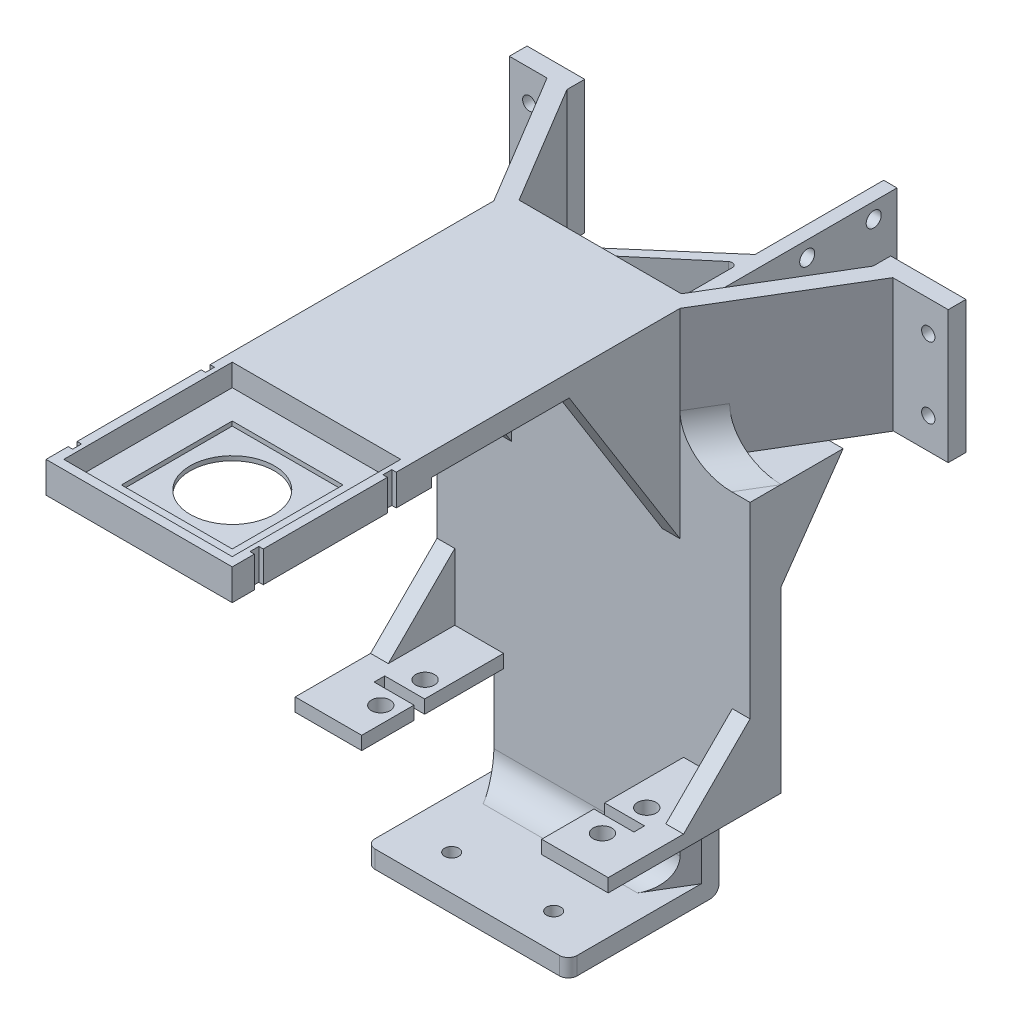
SolidWorks part; units mm, degrees
ref_plane "前视基准面" through (0, 0, 0) normal (0, 0, 1) x (1, 0, 0)
ref_plane "上视基准面" through (0, 0, 0) normal (0, 1, 0) x (1, 0, 0)
ref_plane "右视基准面" through (0, 0, 0) normal (1, 0, 0) x (0, 0, -1)
other "Configuration Table"
sketch "草图1" plane through (0, 0, 0) normal (0, 0, 1) x (1, 0, 0)
  line L0 (0, 22.8958) -> (0, -22.7413) construction
  line L1 (-34.5, 14.6332) -> (-47.5, 14.6332)
  line L2 (-47.5, 14.6332) -> (-47.5, -15.3668)
  line L3 (-47.5, -15.3668) -> (-34.5, -15.3668)
  line L5 (-37.5, 29.7319) -> (-37.5, -30.5186) construction
  line L6 (-34.5, 14.6332) -> (-34.5, -15.3668)
  line L11 (38.5, 14.6332) -> (51.5, 14.6332)
  line L12 (51.5, 14.6332) -> (51.5, -15.2668)
  line L13 (51.5, -15.2668) -> (38.5, -15.2668)
  line L14 (38.5, -15.2668) -> (38.5, 14.6332)
  circle A0 centre (-43, 7.6832) radius 1.5
  circle A1 centre (-43, -8.3168) radius 1.5
  circle A4 centre (47, -8.3168) radius 1.5
  circle A5 centre (47, 7.6832) radius 1.5
  dimension "D3" = 3
  dimension "D4" = 6.95
  dimension "D5" = 16
  dimension "D6" = 3
  dimension "D1" = 3
  dimension "D9" = 90
  dimension "D10" = 3
  dimension "D11" = 4.5
  dimension "D12" = 4.5
  dimension "D13" = 8.5
  dimension "D14" = 6.95
  dimension "D2" = 30
  dimension "D7" = 37.5
  dimension "D8" = 3
extrude "凸台-拉伸1" add sketch "草图1" along normal blind 4
sketch "草图2" plane through (0, 0, 0) normal (0, 1, 0) x (1, 0, 0)
  line L0 (0, 28.3363) -> (0, -34) construction
  line L1 (-39, -4) -> (-21, -34)
  line L2 (-34.5, -4) -> (-47.5, -4) construction
  line L3 (-21, -34) -> (21, -34)
  line L4 (-34.5, -4) -> (-18.3, -31)
  line L5 (-18.3, -31) -> (18.3, -31)
  line L6 (-39, -4) -> (-34.5, -4)
  line L7 (39, -4) -> (34.5, -4)
  line L8 (39, -4) -> (21, -34)
  line L9 (34.5, -4) -> (18.3, -31)
  point P7 (-41, -4)
  point P14 (0, -31)
  dimension "D1" = 21
  dimension "D2" = 30
  dimension "D3" = 2
  dimension "D4" = 3
extrude "凸台-拉伸2" add sketch "草图2" along normal up to surface and the other way up to surface up to face at (-41, 14.6332, 2) other way up to face at (-41, -15.3668, 2)
sketch "草图6" plane through (0, -15.3668, 0) normal (0, -1, 0) x (1, 0, 0)
  line L1 (-21, 31) -> (21.0707, 31)
  line L3 (-18.3, 31) -> (18.3, 31) construction
  line L5 (-21, 34) -> (21, 34)
  line L6 (-21, 34) -> (-22.8, 31)
  line L7 (-21, 34) -> (-39, 4) construction
  line L8 (-22.8, 31) -> (-21, 31)
  line L9 (21.0707, 31) -> (22.8, 31)
  line L10 (39, 4) -> (21, 34) construction
  line L11 (22.8, 31) -> (21, 34)
extrude "凸台-拉伸4" add sketch "草图6" along normal blind 87
sketch "草图8" plane through (0, 0, 34) normal (0, 0, 1) x (1, 0, 0)
  line L0 (-22.8, -102.3668) -> (-22.8, -98.3668)
  line L1 (-22.8, -102.3668) -> (-22.8, -15.3668) construction
  line L2 (-22.8, -98.3668) -> (22.8, -98.3668)
  line L3 (22.8, -102.3668) -> (22.8, -15.3668) construction
  line L4 (22.8, -98.3668) -> (22.8, -102.3668)
  line L5 (22.8, -102.3668) -> (-22.8, -102.3668)
  dimension "D1" = 4
extrude "凸台-拉伸5" add sketch "草图8" along normal blind 30 from offset 3 offset against normal yes
fillet "圆角1" radius 6 1 edges at (0, -98.3668, 34)
sketch "草图10" plane through (0, 0, 31) normal (0, 0, -1) x (-1, 0, 0)
  line L0 (0, 22.2529) -> (0, -15.95) construction
  line L1 (-13.945, 9.6332) -> (-13.945, -12.3668)
  line L3 (18.3, 14.6332) -> (-18.3, 14.6332) construction
  line L4 (-13.945, -12.3668) -> (-16.945, -12.3668)
  line L5 (-16.945, -12.3668) -> (-16.945, 9.6332)
  line L6 (-16.945, 9.6332) -> (-13.945, 9.6332)
  dimension "D1" = 13.945
  dimension "D2" = 5
  dimension "D3" = 22
  dimension "D4" = 3
extrude "凸台-拉伸6" add sketch "草图10" along normal blind 50
sketch "草图13" plane through (13.945, 0, 0) normal (-1, 0, 0) x (0, 0, 1)
  line L1 (-11.75, -47.2714) -> (-11.75, 9.6332) construction
  line L2 (-11.75, -143.0278) -> (-11.75, -111.0278) construction
  line L3 (-19, 9.6332) -> (31, 9.6332) construction
  line L4 (-0.75, -113.0828) -> (-0.75, 9.6332) construction
  line L5 (-19, -1.3668) -> (-27.146, -1.3668) construction
  line L6 (-19, -12.3668) -> (-19, 9.6332) construction
  line L7 (-6.25, -1.9157) -> (-6.25, -9.7031) construction
  circle A0 centre (-13.75, 6.1332) radius 1.7
  circle A1 centre (-13.75, -8.8668) radius 1.7
  circle A2 centre (1.25, 6.1332) radius 1.7
  circle A3 centre (1.25, -8.8668) radius 1.7
  point P21 (-23.073, -1.3668)
  dimension "D1" = 3.4
  dimension "D4" = 7.5
  dimension "D5" = 15
  dimension "D6" = 15
  dimension "D7" = 7.5
  dimension "D2" = 15
  dimension "D3" = 15
  dimension "D8" = 5.5
extrude "切除-拉伸3" cut sketch "草图13" against normal blind 4
fillet "圆角3" radius 6 1 edges at (13.945, -1.3668, 31)
sketch "草图14" plane through (0, -98.3668, 0) normal (0, 1, 0) x (1, 0, 0)
  line L0 (0, -62.8301) -> (0, -20.3908) construction
  line L2 (22.8, -61) -> (-22.8, -61) construction
  circle A0 centre (-11.5, -53) radius 1.6
  circle A1 centre (11.5, -53) radius 1.6
  dimension "D1" = 3.2
  dimension "D2" = 11.5
  dimension "D3" = 3.2
  dimension "D4" = 11.5
  dimension "D5" = 8
extrude "切除-拉伸4" cut sketch "草图14" against normal blind 10
sketch "草图15" plane through (0, 0, 31) normal (0, 0, -1) x (-1, 0, 0)
  line L24 (18.8, -72.6668) -> (18.8, -75.6668)
  line L25 (18.8, -75.6668) -> (33.8, -75.6668)
  line L26 (33.8, -75.6668) -> (33.8, -72.6668)
  line L27 (33.8, -72.6668) -> (18.8, -72.6668)
  line L28 (-21.8, -72.6668) -> (-21.8, -75.6668)
  line L29 (-21.8, -75.6668) -> (-36.8, -75.6668)
  line L30 (-36.8, -75.6668) -> (-36.8, -72.6668)
  line L31 (-36.8, -72.6668) -> (-21.8, -72.6668)
  dimension "D2" = 3
sketch "草图22" plane through (0, 0, 34) normal (0, 0, 1) x (1, 0, 0)
  line L0 (-21, 14.6332) -> (-21, 9.6332)
  line L1 (-21, 14.6332) -> (-21, -92.3668) construction
  line L2 (-21, 9.6332) -> (21, 9.6332)
  line L3 (21, 14.6332) -> (21, -92.3668) construction
  line L4 (21, 9.6332) -> (21, 14.6332)
  line L5 (21, 14.6332) -> (-21, 14.6332)
  dimension "D1" = 5
extrude "凸台-拉伸13" add sketch "草图22" along normal blind 90
sketch "草图23" plane through (0, 14.6332, 0) normal (0, 1, 0) x (1, 0, 0)
  line L0 (0, -76.1625) -> (0, -150.2681) construction
  line L1 (-19, -95) -> (19, -95)
  line L2 (19, -95) -> (19, -133)
  line L3 (19, -133) -> (-19, -133)
  line L4 (21, -124) -> (-21, -124) construction
  line L5 (-19, -95) -> (-19, -133)
  line L6 (-21, -93) -> (-21, -135)
  line L7 (21, -135) -> (-21, -135)
  line L8 (21, -93) -> (21, -135)
  line L9 (-21, -93) -> (21, -93)
  point P10 (0, -95)
  point P11 (0, -133)
  dimension "D1" = 38
  dimension "D2" = 19
  dimension "D3" = 9
  dimension "D4" = 2
extrude "凸台-拉伸14" add sketch "草图23" against normal blind 5
sketch "草图24" plane through (0, 14.6332, 0) normal (0, 1, 0) x (1, 0, 0)
  line L0 (0, -116.507) -> (0, -139.6912) construction
  line L1 (-19, -133) -> (19, -133)
  line L2 (19, -133) -> (19, -95)
  line L3 (19, -95) -> (-19, -95)
  line L4 (-19, -95) -> (-19, -133)
  dimension "D1" = 38
extrude "切除-拉伸6" cut sketch "草图24" against normal blind 5
sketch "草图26" plane through (0, 0, 95) normal (0, 0, 1) x (1, 0, 0)
  line L0 (-21, 9.6332) -> (-21, 7.6332)
  line L1 (-21, 9.6332) -> (-21, -92.3668) construction
  line L2 (-21, 7.6332) -> (21, 7.6332)
  line L3 (21, 9.6332) -> (21, -92.3668) construction
  line L4 (21, 7.6332) -> (21, 9.6332)
  line L5 (21, 9.6332) -> (-21, 9.6332)
  dimension "D1" = 2
extrude "凸台-拉伸17" add sketch "草图26" along normal blind 40 and the other way blind 5
sketch "草图27" plane through (0, 9.6332, 0) normal (0, 1, 0) x (1, 0, 0)
  line L0 (-19, -114) -> (19, -114) construction
  line L1 (-19, -95) -> (-19, -133) construction
  line L2 (19, -133) -> (19, -95) construction
  line L3 (0, -95) -> (0, -133) construction
  line L4 (19, -95) -> (-19, -95) construction
  line L5 (-19, -133) -> (19, -133) construction
  line L7 (12.5, -126.5) -> (-12.5, -126.5)
  line L8 (12.5, -126.5) -> (12.5, -101.5)
  line L9 (12.5, -101.5) -> (-12.5, -101.5)
  line L10 (-12.5, -126.5) -> (-12.5, -101.5)
  line L11 (12.5, -126.5) -> (-12.5, -101.5) construction
  line L12 (12.5, -101.5) -> (-12.5, -126.5) construction
  point P12 (0, -114)
  dimension "D1" = 25
  dimension "D2" = 25
extrude "切除-拉伸7" cut sketch "草图27" against normal blind 1
sketch "草图28" plane through (0, 8.6332, 0) normal (0, 1, 0) x (1, 0, 0)
  circle A0 centre (0, -114) radius 9.5
  dimension "D1" = 19
extrude "切除-拉伸8" cut sketch "草图28" against normal blind 1
sketch "草图29" plane through (-21, 0, 0) normal (-1, 0, 0) x (0, 0, 1)
  line L0 (34, -30.3668) -> (59, 9.6332)
  line L1 (34, 9.6332) -> (34, -92.3668) construction
  line L2 (90, 9.6332) -> (34, 9.6332) construction
  line L3 (59, 9.6332) -> (34, 9.6332)
  line L4 (34, 9.6332) -> (34, -30.3668)
  dimension "D1" = 40
  dimension "D2" = 25
extrude "凸台-拉伸18" add sketch "草图29" against normal blind 4
sketch "草图30" plane through (21, 0, 0) normal (1, 0, 0) x (0, 0, -1)
  line L0 (-59, 9.6332) -> (-34, -30.3668)
  line L1 (-34, -30.3668) -> (-34, 9.6332)
  line L2 (-34, 9.6332) -> (-59, 9.6332)
extrude "凸台-拉伸19" add sketch "草图30" against normal blind 4
fillet "圆角4" radius 6 1 edges at (0, 9.6332, 34)
sketch "草图31" plane through (-21, 0, 0) normal (-1, 0, 0) x (0, 0, 1)
  line L0 (98, 14.6332) -> (98, 7.6332)
  line L1 (135, 14.6332) -> (34, 14.6332) construction
  line L2 (90, 7.6332) -> (135, 7.6332) construction
  line L3 (98, 7.6332) -> (100, 7.6332)
  line L4 (100, 7.6332) -> (100, 14.6332)
  line L5 (100, 14.6332) -> (98, 14.6332)
  line L6 (114, 30.4335) -> (114, -19.5291) construction
  line L7 (135, 7.6332) -> (135, 14.6332) construction
  line L8 (128, 14.6332) -> (128, 7.6332)
  line L9 (128, 7.6332) -> (130, 7.6332)
  line L10 (130, 7.6332) -> (130, 14.6332)
  line L11 (130, 14.6332) -> (128, 14.6332)
  dimension "D1" = 2
  dimension "D2" = 21
  dimension "D3" = 14
  dimension "D4" = 2
  dimension "D5" = 14
extrude "切除-拉伸9" cut sketch "草图31" against normal blind 1
sketch "草图32" plane through (21, 0, 0) normal (1, 0, 0) x (0, 0, -1)
  line L0 (-114, 32.0823) -> (-114, -14.4339) construction
  line L1 (-135, 7.6332) -> (-135, 14.6332) construction
  line L2 (-100, 7.6332) -> (-100, 14.6332)
  line L3 (-90, 7.6332) -> (-135, 7.6332) construction
  line L4 (-135, 14.6332) -> (-34, 14.6332) construction
  line L5 (-100, 14.6332) -> (-98, 14.6332)
  line L6 (-98, 14.6332) -> (-98, 7.6332)
  line L7 (-98, 7.6332) -> (-100, 7.6332)
  line L12 (-130, 14.6332) -> (-130, 7.6332)
  line L13 (-130, 7.6332) -> (-128, 7.6332)
  line L14 (-128, 7.6332) -> (-128, 14.6332)
  line L15 (-128, 14.6332) -> (-130, 14.6332)
  dimension "D1" = 21
  dimension "D2" = 2
  dimension "D3" = 2
  dimension "D4" = 14
extrude "切除-拉伸10" cut sketch "草图32" against normal blind 1
sketch "草图34" plane through (0, 14.6332, 0) normal (0, 1, 0) x (1, 0, 0)
  line L0 (38.5, 0) -> (34.5183, 0)
  line L1 (34.5183, 20.75) -> (34.5183, -7.25) construction
  line L2 (34.5183, 0) -> (34.5183, -4)
  line L3 (34.5, -4) -> (39, -4) construction
  line L4 (34.5183, -4) -> (38.5, -4)
  line L5 (38.5, -4) -> (38.5, 0)
extrude "凸台-拉伸20" add sketch "草图34" against normal up to surface (29.9 mm away) up to face at (45, -15.2668, 2)
extrude "凸台-拉伸29" add sketch "草图15" against normal blind 35
sketch "草图45" plane through (-33.8, 0, 0) normal (-1, 0, 0) x (0, 0, 1)
  line L0 (31, -75.6668) -> (31, -25.6668)
  line L1 (31, -72.6668) -> (31, -15.3668) construction
  line L2 (31, -25.6668) -> (34, -25.6668)
  line L3 (34, -30.3668) -> (34, -72.6668) construction
  line L4 (34, -25.6668) -> (34, -75.6668)
  line L5 (34, -75.6668) -> (31, -75.6668)
  dimension "D1" = 50
extrude "凸台-拉伸30" add sketch "草图45" against normal up to surface (12.8 mm away) up to face at (-21.1491, -88.3353, 33.7515)
sketch "草图46" plane through (36.8, 0, 0) normal (1, 0, 0) x (0, 0, -1)
  line L0 (-31, -75.6668) -> (-31, -25.6668)
  line L1 (-31, -72.6668) -> (-31, -15.3668) construction
  line L2 (-31, -25.6668) -> (-34, -25.6668)
  line L3 (-34, -30.3668) -> (-34, -92.3668) construction
  line L4 (-34, -25.6668) -> (-34, -75.6668)
  line L5 (-34, -75.6668) -> (-31, -75.6668)
  dimension "D1" = 50
extrude "凸台-拉伸31" add sketch "草图46" against normal up to surface (15.8 mm away) up to face at (25.6112, -48.7778, 26.3147)
sketch "草图47" plane through (0, -72.6668, 0) normal (0, 1, 0) x (1, 0, 0)
  line L0 (-33.8, -66) -> (-18.8, -66) construction
  line L1 (-22.5, -58) -> (-22.5, -48) construction
  line L2 (-22.5, -53) -> (25.8541, -53) construction
  line L3 (21.8, -54.2) -> (30.8, -54.2)
  line L4 (21.8, -66) -> (21.8, -34) construction
  line L5 (30.8, -54.2) -> (30.8, -51.8)
  line L6 (30.8, -51.8) -> (21.8, -51.8)
  line L7 (21.8, -51.8) -> (21.8, -54.2)
  line L8 (-18.8, -66) -> (-18.8, -34) construction
  line L9 (-18.8, -51.8) -> (-27.8, -51.8)
  line L10 (-27.8, -51.8) -> (-27.8, -54.2)
  line L11 (-27.8, -54.2) -> (-18.8, -54.2)
  line L12 (-18.8, -54.2) -> (-18.8, -51.8)
  circle A0 centre (-22.5, -48) radius 2.1
  circle A1 centre (-22.5, -58) radius 2.1
  circle A2 centre (27.5, -48) radius 2.1
  circle A3 centre (27.5, -58) radius 2.1
  dimension "D1" = 8
  dimension "D2" = 4.2
  dimension "D3" = 4.2
  dimension "D4" = 10
  dimension "D8" = 50
  dimension "D9" = 3.7
  dimension "D10" = 50
  dimension "D11" = 4.2
  dimension "D12" = 4.2
  dimension "D5" = 1.2
  dimension "D6" = 1.2
  dimension "D7" = 9
  dimension "D13" = 1.2
  dimension "D14" = 1.2
  dimension "D15" = 9
extrude "切除-拉伸13" cut sketch "草图47" against normal blind 4
sketch "草图48" plane through (-33.8, 0, 0) normal (-1, 0, 0) x (0, 0, 1)
  line L0 (34, -57.6668) -> (49, -72.6668)
  line L1 (34, -72.6668) -> (34, -25.6668) construction
  line L2 (66, -72.6668) -> (34, -72.6668) construction
  line L3 (49, -72.6668) -> (34, -72.6668)
  line L4 (34, -72.6668) -> (34, -57.6668)
  dimension "D1" = 15
  dimension "D2" = 15
extrude "凸台-拉伸32" add sketch "草图48" against normal blind 4
sketch "草图49" plane through (36.8, 0, 0) normal (1, 0, 0) x (0, 0, -1)
  line L0 (-34, -57.6668) -> (-49, -72.6668)
  line L1 (-49, -72.6668) -> (-34, -72.6668)
  line L2 (-34, -72.6668) -> (-34, -57.6668)
extrude "凸台-拉伸33" add sketch "草图49" against normal blind 4
sketch "草图50" plane through (0, 9.6332, 0) normal (0, 1, 0) x (1, 0, 0)
  line L0 (-7.3, -31) -> (13.945, -13)
  line L1 (-18.3, -31) -> (18.3, -31) construction
  line L2 (13.945, 19) -> (13.945, -25) construction
  line L4 (-10.3, -31) -> (13.945, -10)
  line L5 (13.945, -13) -> (13.945, -10)
  line L6 (-10.3, -31) -> (-7.3, -31)
  dimension "D1" = 3
  dimension "D2" = 3
  dimension "D3" = 8
  dimension "D4" = 21
extrude "凸台-拉伸34" add sketch "草图50" against normal up to surface (22 mm away) up to face at (14.1935, -12.3668, 10.0485)
fillet "圆角9" radius 2 1 edges at (-7.3, -1.3668, 31)
fillet "圆角10" radius 1 1 edges at (13.945, -1.3668, 13)
sketch "草图51" plane through (36.8, 0, 0) normal (1, 0, 0) x (0, 0, -1)
  line L0 (-31, -25.6668) -> (-31, -15.3668)
  line L4 (-34, -25.6668) -> (-31, -25.6668)
  line L5 (-31, -15.3668) -> (-34, -15.3668)
  line L6 (-34, -75.6668) -> (-34, -92.3668) construction
  line L7 (-34, -15.3668) -> (-34, -25.6668)
extrude "凸台-拉伸35" add sketch "草图51" against normal up to surface (15.8 mm away) up to face at (29.2286, -9.7239, 20.2857)
sketch "草图52" plane through (-33.8, 0, 0) normal (-1, 0, 0) x (0, 0, 1)
  line L0 (34, -25.6668) -> (31, -25.6668)
  line L1 (31, -25.6668) -> (31, -15.3668)
  line L2 (31, -15.3668) -> (34, -15.3668)
  line L3 (34, -75.6668) -> (34, -92.3668) construction
  line L4 (34, -15.3668) -> (34, -25.6668)
extrude "凸台-拉伸36" add sketch "草图52" against normal up to surface (12.8 mm away) up to face at (-21.1491, -88.3353, 33.7515)
sketch "草图55" plane through (0, 0, 31) normal (0, 0, -1) x (-1, 0, 0)
  line L0 (33.8, -15.3668) -> (-36.8, -15.3668)
  line L1 (-36.8, -15.3668) -> (-36.8, -75.6668)
  line L2 (-36.8, -75.6668) -> (33.8, -75.6668)
  line L3 (33.8, -75.6668) -> (33.8, -15.3668)
  point P0 (0, 0)
extrude "凸台-拉伸39" add sketch "草图55" along normal blind 4
fillet "圆角11" radius 10 2 edges at (-23.1, -15.3668, 30.5) (23.1, -15.3668, 30.5)
sketch "草图58" plane through (36.8, 0, 0) normal (1, 0, 0) x (0, 0, -1)
  line L0 (-27, -15.3667) -> (-13, -15.3668)
  line L1 (-4, -15.3668) -> (-27, -15.3668) construction
  line L2 (-13, -15.3668) -> (-27, -35.3667)
  line L3 (-27, -15.3667) -> (-27, -75.6668) construction
  line L4 (-27, -35.3667) -> (-27, -15.3667)
  dimension "D1" = 14
  dimension "D2" = 20
extrude "凸台-拉伸41" add sketch "草图58" against normal up to surface (70.6 mm away) up to face at (-33.8, -50.0214, 41.8851)
sketch "草图61" plane through (22.8, 0, 0) normal (1, 0, 0) x (0, 0, -1)
  line L0 (-27, -75.6668) -> (-27, -102.3668)
  line L1 (-61, -102.3668) -> (-31, -102.3668) construction
  line L2 (-27, -75.6668) -> (-31, -75.6668)
  line L3 (-31, -75.6668) -> (-31, -102.3668)
  line L4 (-31, -102.3668) -> (-27, -102.3668)
extrude "凸台-拉伸42" add sketch "草图61" against normal up to surface (45.6 mm away) up to face at (-22.8, -100.3668, 46)
fillet "圆角12" radius 2 3 edges at (-22.8, -100.3668, 61) (0, -102.3668, 27) (22.8, -100.3668, 61)
